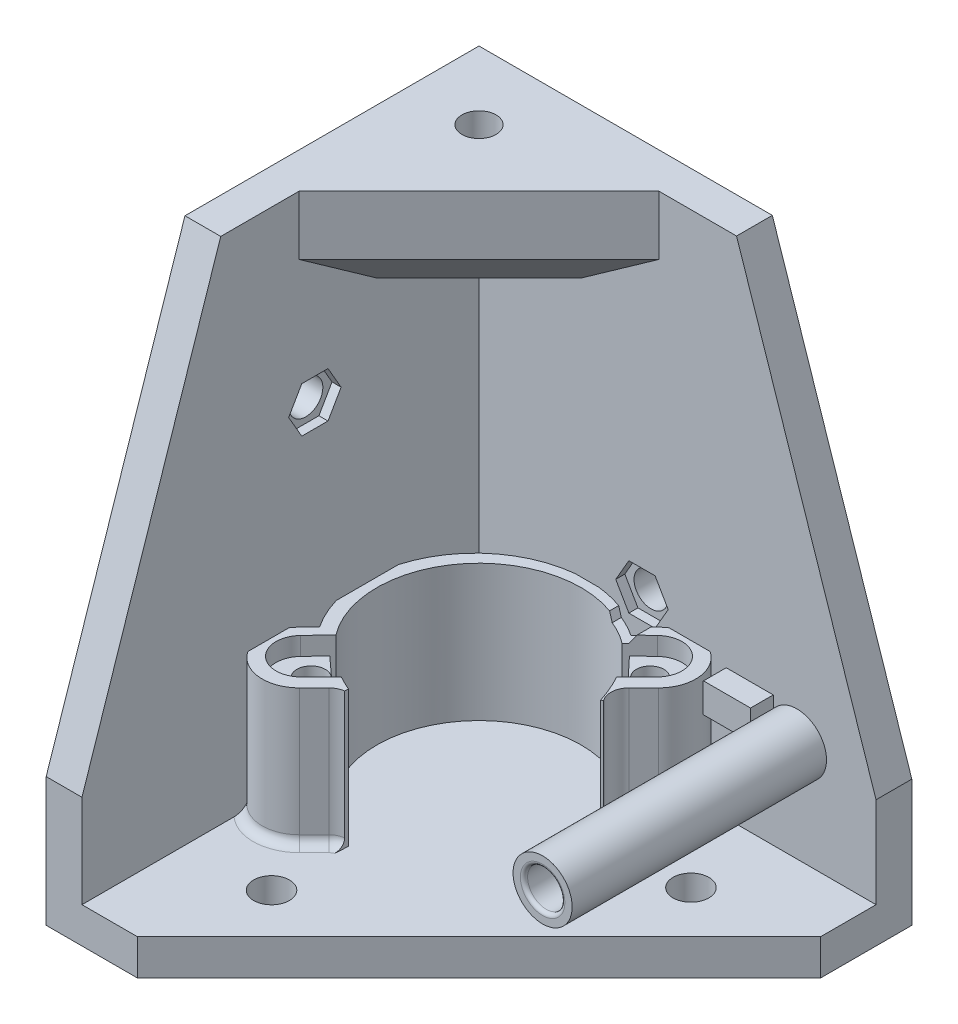
SolidWorks part; units mm, degrees
ref_plane "Front" through (0, 0, 0) normal (0, 0, 1) x (1, 0, 0)
ref_plane "Top" through (0, 0, 0) normal (0, 1, 0) x (1, 0, 0)
ref_plane "Right" through (0, 0, 0) normal (1, 0, 0) x (0, 0, -1)
sketch "Sketch1" plane through (0, 0, 0) normal (0, 1, 0) x (1, 0, 0)
  line L0 (0, 0) -> (0, 60.5)
  line L1 (0, -55) -> (0, 55) construction
  line L2 (0, 60.5) -> (60.5, 60.5)
  line L3 (60.5, 60.5) -> (60.5, 47.75)
  line L4 (60.5, 47.75) -> (12.75, 0)
  line L5 (-55, 0) -> (55, 0) construction
  line L6 (12.75, 0) -> (0, 0)
  dimension "D1" = 60.5
  dimension "D2" = 12.75
extrude "Boss-Extrude1" add sketch "Sketch1" along normal blind 5
sketch "Sketch4" plane through (0, 0, 0) normal (-1, 0, 0) x (0, 0, 1)
  line L0 (-60.5, 5) -> (-60.5, 76.1962)
  line L1 (-60.5, 76.1962) -> (-19.4, 76.1962)
  line L2 (-19.4, 76.1962) -> (0, 18.0048)
  line L3 (0, 18.0048) -> (0, 5)
  line L4 (0, -2.75) -> (0, 2.75) construction
  line L5 (-60.5, 5) -> (0, 5) construction
  line L6 (-60.5, 5) -> (0, 5)
  dimension "D1" = 71.1962
  dimension "D2" = 41.1
  dimension "D3" = 61.34
extrude "Boss-Extrude2" add sketch "Sketch4" against normal blind 5
sketch "Sketch5" plane through (0, 0, -60.5) normal (0, 0, -1) x (-1, 0, 0)
  line L0 (0, 76.1962) -> (-41, 76.1962)
  line L1 (-41, 76.1962) -> (-60.5, 17.7009)
  line L2 (-60.5, 17.7009) -> (-60.5, 5)
  line L6 (-60.5, 0) -> (0, 0)
  line L7 (0, 0) -> (0, 76.1962)
  line L8 (0, 76.1962) -> (-5, 76.1962)
  line L9 (-5, 76.1962) -> (-5, 5)
  line L10 (-5, 5) -> (-60.5, 5)
  line L11 (-60.5, 5) -> (-60.5, 0)
  line L12 (-60.5, 0) -> (0, 0)
  line L13 (0, 0) -> (0, 76.1962)
  line L14 (0, 76.1962) -> (-5, 76.1962)
  line L15 (-5, 76.1962) -> (-5, 5)
  line L16 (-5, 5) -> (-60.5, 5)
  line L17 (-60.5, 5) -> (-60.5, 0)
  line M13 (-5, 76.1962) -> (-5, 5)
  line M14 (-5, 5) -> (-60.5, 5)
  dimension "D2" = 41
  dimension "D3" = 61.66
  dimension "D1" = 0
extrude "Boss-Extrude3" add sketch "Sketch5" against normal blind 5 contours L1 L2 L0 M14 M13 region at (29.1655, 37.8824, -60.5)
sketch "Sketch6" plane through (0, 5, 0) normal (0, 1, 0) x (1, 0, 0)
  line L0 (60.5, 60.5) -> (0, 60.5) construction
  line L4 (0, 19.4) -> (0, 0)
  line L5 (60.5, 55.5) -> (5, 55.5)
  line L6 (5, 55.5) -> (5, 0)
  line L7 (5, 0) -> (12.75, 0)
  line L8 (12.75, 0) -> (60.5, 47.75)
  line L9 (60.5, 47.75) -> (60.5, 55.5)
  line L10 (60.5, 55.5) -> (5, 55.5)
  line L11 (5, 55.5) -> (5, 0)
  line L12 (5, 0) -> (12.75, 0)
  line L13 (12.75, 0) -> (60.5, 47.75)
  line L14 (60.5, 47.75) -> (60.5, 55.5)
  line L15 (0, 0) -> (5, 0)
  line L16 (5, 0) -> (5, 19.4)
  line L17 (5, 19.4) -> (0, 19.4)
  line L18 (0, 19.4) -> (0, 0)
  line L19 (0, 0) -> (5, 0)
  line L20 (5, 0) -> (5, 19.4)
  line L21 (5, 19.4) -> (0, 19.4)
  line L24 (0, 60.5) -> (0, 19.4)
  line L25 (0, 19.4) -> (5, 19.4)
  line L26 (5, 19.4) -> (5, 55.5)
  line L27 (5, 55.5) -> (41, 55.5)
  line L28 (41, 55.5) -> (41, 60.5)
  line L29 (41, 60.5) -> (0, 60.5)
  line L30 (0, 60.5) -> (0, 19.4)
  line L31 (0, 19.4) -> (5, 19.4)
  line L32 (5, 19.4) -> (5, 55.5)
  line L33 (5, 55.5) -> (41, 55.5)
  line L34 (41, 55.5) -> (41, 60.5)
  line L35 (41, 60.5) -> (0, 60.5)
  circle A0 centre (16.5, 15) radius 2.5
  circle A1 centre (45.5, 44.625) radius 2.5
  dimension "D1" = 5
  dimension "D2" = 5
  dimension "D3" = 0
  dimension "D4" = 15
  dimension "D6" = 16.5
  dimension "D7" = 15
  dimension "D9" = 15.875
  dimension "D5" = 0
  dimension "D8" = 0
extrude "Cut-Extrude1" cut sketch "Sketch6" against normal through all contours A0 | A1 region at (16.5, 5, -15) region at (45.5, 5, -44.625)
sketch "Sketch9" plane through (0, 0, -55.5) normal (0, 0, 1) x (1, 0, 0)
  line L1 (5, 76.1962) -> (5, 5) construction
  line L5 (0, 0) -> (60.5, 0)
  line L6 (0, 76.1962) -> (0, 0)
  line L7 (41, 76.1962) -> (0, 76.1962)
  line L8 (60.5, 17.7009) -> (41, 76.1962)
  line L9 (60.5, 0) -> (60.5, 17.7009)
  line L10 (0, 0) -> (60.5, 0)
  line L11 (0, 76.1962) -> (0, 0)
  line L12 (41, 76.1962) -> (0, 76.1962)
  line L13 (60.5, 17.7009) -> (41, 76.1962)
  line L14 (60.5, 0) -> (60.5, 17.7009)
  line L15 (49.45, 19.0462) -> (49.45, 3.6199) construction
  circle A0 centre (49.45, 19.0462) radius 4.1275
  circle A1 centre (49.45, 19.0462) radius 2.6035
  dimension "D2" = 5.207
  dimension "D3" = 1.524
  dimension "D4" = 57.15
  dimension "D5" = 44.45
  dimension "D1" = 0
extrude "Boss-Extrude5" add sketch "Sketch9" along normal blind 35.56 contours A1 A0 region at (45.4392, 19.0462, -55.5)
fillet "Fillet1" radius 0.508 1 edges at (52.0535, 19.0462, -19.94)
sketch "Sketch14" plane through (0, 5, 0) normal (0, 1, 0) x (1, 0, 0)
  line L0 (13.4627, 27.5396) -> (14.7681, 26.7924)
  line L1 (12.75, 0) -> (60.5, 47.75) construction
  line L2 (36.625, 23.875) -> (5, 55.5) construction
  line L3 (5, 55.5) -> (60.5, 55.5) construction
  line L4 (32.9604, 47.0373) -> (33.7076, 45.7319)
  line L5 (14.8281, 26.8523) -> (11.8274, 23.8516)
  line L6 (6.723, 28.8027) -> (9.1327, 31.3641)
  line L7 (33.6477, 45.6719) -> (36.6484, 48.6726)
  line L8 (31.6973, 53.777) -> (29.1359, 51.3673)
  line L9 (15.0744, 24.4582) -> (13.006, 22.3898)
  line L10 (5.6561, 29.7396) -> (7.0609, 31.1444)
  line L11 (36.0418, 45.4256) -> (38.1102, 47.494)
  line L12 (30.7604, 54.8439) -> (28.83, 52.9135)
  line L13 (18.1324, 24.8665) -> (30.5234, 17.7734)
  line L14 (35.6335, 42.3676) -> (42.7266, 29.9766)
  line L15 (31.7409, 18.9909) -> (18.852, 25.7543)
  line L16 (41.5091, 28.7591) -> (34.7457, 41.648)
  line L17 (16.5689, 25.6946) -> (16.5343, 25.1798)
  line L18 (34.7457, 41.648) -> (35.7996, 42.0774)
  circle A0 centre (20.5607, 39.9393) radius 14.2875
  arc A1 (11.8274, 23.8516) -> (6.723, 28.8027) centre (9.3129, 26.3661) cw
  arc A2 (36.6484, 48.6726) -> (31.6973, 53.777) centre (34.1339, 51.1871) ccw
  arc A3 (13.006, 22.3898) -> (5.6561, 29.7396) centre (9.3311, 26.0647) cw
  arc A4 (38.1102, 47.494) -> (30.7604, 54.8439) centre (34.4353, 51.1689) ccw
  arc A5 (7.0609, 31.1444) -> (28.83, 52.9135) centre (20.0709, 39.9035) cw
  arc A6 (36.0418, 45.4256) -> (35.6335, 42.3676) centre (37.8378, 43.6295) ccw
  arc A7 (15.0744, 24.4582) -> (18.1324, 24.8665) centre (16.8705, 22.6622) cw
  arc A9 (33.8602, 45.8844) -> (36.3595, 38.5726) centre (13.6025, 34.877) cw
  arc A10 (14.6156, 26.6398) -> (21.9274, 24.1405) centre (25.623, 46.8975) ccw
  point P40 (34.6689, 44.0527)
  point P43 (16.4473, 25.8311)
  line M13 (60.5, 55.5) -> (5, 55.5)
  line M14 (5, 55.5) -> (5, 0)
  line M16 (12.75, 0) -> (60.5, 47.75)
  dimension "D1" = 28.575
  dimension "D2" = 3.556
  dimension "D3" = 2.54
extrude "Boss-Extrude6" add sketch "Sketch14" along normal blind 19.05 contours L2 A0 L5 A1 L6 A5 L10 A3 L9 A7 L13 M16 M14 | L2 L14 A6 L11 A4 L12 A5 A0 L8 A2 L7 M16 M13 region at (7.691, 5, -30.3062) region at (10.0875, 5, -50.8829)
sketch "Sketch15" plane through (0, 76.1962, 0) normal (0, 1, 0) x (1, 0, 0)
  line L0 (5, 30.3375) -> (30.1625, 55.5)
  line L1 (0, -33.275) -> (0, 33.275) construction
  line L2 (41, 60.5) -> (0, 60.5) construction
  line L6 (0, 60.5) -> (0, 19.4)
  line L7 (0, 19.4) -> (5, 19.4)
  line L8 (5, 19.4) -> (5, 55.5)
  line L9 (5, 55.5) -> (41, 55.5)
  line L10 (41, 55.5) -> (41, 60.5)
  line L11 (41, 60.5) -> (0, 60.5)
  line L13 (0, 19.4) -> (5, 19.4)
  line L14 (5, 30.3375) -> (5, 55.5)
  line L15 (5, 55.5) -> (30.1625, 55.5)
  line L16 (41, 55.5) -> (41, 60.5)
  circle A0 centre (9.525, 50.975) radius 2.3812
  line M11 (5, 19.4) -> (5, 55.5)
  line M12 (5, 55.5) -> (41, 55.5)
  dimension "D3" = 4.7625
  dimension "D4" = 9.525
  dimension "D5" = 9.525
  dimension "D2" = 45
  dimension "D1" = 0
extrude "Boss-Extrude7" add sketch "Sketch15" against normal blind 15.875 contours L0 A0 M11 M12 region at (13.6178, 76.1962, -46.8822)
chamfer "Chamfer2" distance 7.62 angle 45 1 edges at (17.5813, 60.3212, -42.9187)
fillet "Fillet2" radius 1.27 7 edges at (39.6065, 5, -51.6871) (37.076, 5, -46.4598) (35.3202, 5, -43.9657) (8.8129, 5, -20.8935) (14.0402, 5, -23.424) (15.745, 5, -24.9392) (35.7165, 5, -42.2225)
sketch "Sketch16" plane through (0, 0, -55.5) normal (0, 0, 1) x (1, 0, 0)
  line L1 (46.1305, 23.2107) -> (38.2864, 23.2107)
  line L2 (46.1305, 23.2107) -> (46.1305, 19.0978)
  line L3 (46.1305, 19.0978) -> (38.2864, 19.0978)
  line L4 (38.2864, 23.2107) -> (38.2864, 19.0978)
extrude "Boss-Extrude8" add sketch "Sketch16" along normal blind 3.175
chamfer "Chamfer3" distance 1.27 angle 45 1 edges at (38.2864, 23.2107, -55.0794)
sketch "Sketch17" plane through (0, 5, 0) normal (0, 1, 0) x (1, 0, 0)
  line L0 (8.716, 30.9212) -> (14.047, 26.0712)
  line L1 (36.625, 23.875) -> (5, 55.5) construction
  line L2 (12.75, 0) -> (60.5, 47.75) construction
  line L3 (5, 55.5) -> (18.418, 55.5) construction
  line L4 (5, 55.5) -> (5, 44.2452) construction
  line L5 (29.6632, 51.8634) -> (34.5959, 46.6202)
  line L22 (37.3079, 55.5) -> (31.5627, 55.5)
  line L23 (30.7604, 54.8439) -> (28.83, 52.9135)
  line L24 (21.7238, 55.5) -> (18.418, 55.5)
  line L25 (5, 44.2452) -> (5, 35.5618)
  line L26 (7.0609, 31.1444) -> (5.6561, 29.7396)
  line L27 (5, 28.9373) -> (5, 23.1921)
  line L28 (13.006, 22.3898) -> (15.0744, 24.4582)
  line L29 (16.5343, 25.1798) -> (16.5689, 25.6946)
  line L30 (16.5343, 25.1798) -> (16.5689, 25.6946)
  line L31 (35.539, 41.9712) -> (35.7996, 42.0774)
  line L32 (35.539, 41.9712) -> (35.7996, 42.0774)
  line L33 (14.6156, 26.6398) -> (11.8274, 23.8516)
  line L34 (6.723, 28.8027) -> (9.1327, 31.3641)
  line L35 (29.1359, 51.3673) -> (31.6973, 53.777)
  line L36 (36.6484, 48.6726) -> (33.8602, 45.8844)
  line L40 (35.7996, 42.0774) -> (35.6335, 42.3676)
  line L41 (36.0418, 45.4256) -> (38.1102, 47.494)
  line L43 (37.3079, 55.5) -> (31.5627, 55.5)
  line L44 (30.7604, 54.8439) -> (28.83, 52.9135)
  line L45 (21.7238, 55.5) -> (18.418, 55.5)
  line L46 (5, 44.2452) -> (5, 35.5618)
  line L47 (7.0609, 31.1444) -> (5.6561, 29.7396)
  line L48 (5, 28.9373) -> (5, 23.1921)
  line L49 (13.006, 22.3898) -> (15.0744, 24.4582)
  line L54 (14.6156, 26.6398) -> (11.8274, 23.8516)
  line L55 (6.723, 28.8027) -> (9.1327, 31.3641)
  line L56 (29.1359, 51.3673) -> (31.6973, 53.777)
  line L57 (36.6484, 48.6726) -> (33.8602, 45.8844)
  line L61 (35.7996, 42.0774) -> (35.6335, 42.3676)
  line L62 (36.0418, 45.4256) -> (38.1102, 47.494)
  circle A1 centre (33.6908, 50.7324) radius 2.1828
  circle A2 centre (10.0204, 27.0078) radius 1.9844
  circle A3 centre (33.6908, 50.7324) radius 1.9288
  arc A15 (38.1102, 47.494) -> (37.3079, 55.5) centre (34.4353, 51.1689) ccw
  arc A17 (31.5627, 55.5) -> (30.7604, 54.8439) centre (34.4353, 51.1689) ccw
  arc A18 (28.83, 52.9135) -> (21.7238, 55.5) centre (20.0709, 39.9035) ccw
  arc A19 (18.418, 55.5) -> (5, 44.2452) centre (20.0709, 39.9035) ccw
  arc A20 (5, 35.5618) -> (7.0609, 31.1444) centre (20.0709, 39.9035) ccw
  arc A21 (5.6561, 29.7396) -> (5, 28.9373) centre (9.3311, 26.0647) ccw
  arc A22 (5, 23.1921) -> (13.006, 22.3898) centre (9.3311, 26.0647) ccw
  arc A23 (16.5343, 25.1798) -> (15.0744, 24.4582) centre (16.8705, 22.6622) ccw
  arc A24 (14.6156, 26.6398) -> (16.5689, 25.6946) centre (25.623, 46.8975) ccw
  arc A25 (6.723, 28.8027) -> (11.8274, 23.8516) centre (9.3129, 26.3661) ccw
  arc A26 (29.1359, 51.3673) -> (9.1327, 31.3641) centre (20.5607, 39.9393) ccw
  arc A27 (36.6484, 48.6726) -> (31.6973, 53.777) centre (34.1339, 51.1871) ccw
  arc A28 (35.539, 41.9712) -> (33.8602, 45.8844) centre (13.6025, 34.877) ccw
  arc A29 (36.0418, 45.4256) -> (35.6335, 42.3676) centre (37.8378, 43.6295) ccw
  arc A30 (38.1102, 47.494) -> (37.3079, 55.5) centre (34.4353, 51.1689) ccw
  arc A32 (31.5627, 55.5) -> (30.7604, 54.8439) centre (34.4353, 51.1689) ccw
  arc A33 (28.83, 52.9135) -> (21.7238, 55.5) centre (20.0709, 39.9035) ccw
  arc A34 (18.418, 55.5) -> (5, 44.2452) centre (20.0709, 39.9035) ccw
  arc A35 (5, 35.5618) -> (7.0609, 31.1444) centre (20.0709, 39.9035) ccw
  arc A36 (5.6561, 29.7396) -> (5, 28.9373) centre (9.3311, 26.0647) ccw
  arc A37 (5, 23.1921) -> (13.006, 22.3898) centre (9.3311, 26.0647) ccw
  arc A38 (16.5343, 25.1798) -> (15.0744, 24.4582) centre (16.8705, 22.6622) ccw
  arc A39 (14.6156, 26.6398) -> (16.5689, 25.6946) centre (25.623, 46.8975) ccw
  arc A40 (6.723, 28.8027) -> (11.8274, 23.8516) centre (9.3129, 26.3661) ccw
  arc A41 (29.1359, 51.3673) -> (9.1327, 31.3641) centre (20.5607, 39.9393) ccw
  arc A42 (36.6484, 48.6726) -> (31.6973, 53.777) centre (34.1339, 51.1871) ccw
  arc A43 (35.539, 41.9712) -> (33.8602, 45.8844) centre (13.6025, 34.877) ccw
  arc A44 (36.0418, 45.4256) -> (35.6335, 42.3676) centre (37.8378, 43.6295) ccw
  line M44 (33.8602, 45.8844) -> (36.6484, 48.6726)
  arc M45 (36.6484, 48.6726) -> (31.6973, 53.777) centre (34.1339, 51.1871) ccw
  line M46 (31.6973, 53.777) -> (29.1359, 51.3673)
  line M48 (9.1327, 31.3641) -> (6.723, 28.8027)
  arc M49 (6.723, 28.8027) -> (11.8274, 23.8516) centre (9.3129, 26.3661) ccw
  line M50 (11.8274, 23.8516) -> (14.6156, 26.6398)
  dimension "D2" = 3.9688
  dimension "D3" = 0.254
  dimension "D1" = 0
extrude "Boss-Extrude9" add sketch "Sketch17" along normal offset from surface (16.51 mm away) 2.54 contours L5 A1 M46 M44 M45 | L0 M48 M49 M50 | A1 L5 A3 region at (11.3737, 5, -28.4876) region at (30.7585, 5, -52.737) region at (33.0584, 5, -52.7569) up to face at (20.9693, 24.05, -39.9839)
sketch "Sketch18" plane through (0, 0, 0) normal (-1, 0, 0) x (0, 0, 1)
  line L0 (-60.5, 76.1962) -> (-60.5, 0) construction
  line L1 (33.275, 0) -> (-33.275, 0) construction
  circle A0 centre (-32.56, 49.53) radius 2.3813
  dimension "D1" = 27.94
  dimension "D2" = 49.53
  dimension "D3" = 4.7625
extrude "Cut-Extrude2" cut sketch "Sketch18" against normal up to next
sketch "Sketch19" plane through (0, 0, -60.5) normal (0, 0, -1) x (-1, 0, 0)
  line L0 (0, 33.275) -> (0, -33.275) construction
  line L1 (33.275, 0) -> (-33.275, 0) construction
  circle A0 centre (-27.7812, 26.1937) radius 2.3813
  dimension "D1" = 27.7812
  dimension "D2" = 26.1937
  dimension "D3" = 4.7625
extrude "Cut-Extrude3" cut sketch "Sketch19" against normal up to next
sketch "Sketch20" plane through (0, 0, -55.5) normal (0, 0, 1) x (1, 0, 0)
  line L1 (31.4474, 26.1937) -> (29.6143, 29.3687)
  line L2 (29.6143, 29.3687) -> (25.9482, 29.3687)
  line L3 (25.9482, 29.3687) -> (24.1151, 26.1937)
  line L4 (24.1151, 26.1937) -> (25.9482, 23.0187)
  line L5 (25.9482, 23.0187) -> (29.6143, 23.0187)
  line L6 (29.6143, 23.0187) -> (31.4474, 26.1937)
  circle A0 centre (27.7812, 26.1937) radius 2.3813 construction
  circle A1 centre (27.7812, 26.1937) radius 2.3813
  circle A2 centre (27.7812, 26.1937) radius 3.175 construction
  dimension "D1" = 6.35
extrude "Cut-Extrude4" cut sketch "Sketch20" against normal blind 1.27 and the other way up to vertex (4.1327 mm away) contours L1 L2 L3 L4 L5 L6 other way up to point (29.1359, 24.05, -51.3673)
sketch "Sketch21" plane through (5, 0, 0) normal (1, 0, 0) x (0, 0, -1)
  line L1 (34.3931, 52.705) -> (30.7269, 52.705)
  line L2 (30.7269, 52.705) -> (28.8938, 49.53)
  line L3 (28.8938, 49.53) -> (30.7269, 46.355)
  line L4 (30.7269, 46.355) -> (34.3931, 46.355)
  line L5 (34.3931, 46.355) -> (36.2262, 49.53)
  line L6 (36.2262, 49.53) -> (34.3931, 52.705)
  circle A0 centre (32.56, 49.53) radius 2.3813 construction
  circle A1 centre (32.56, 49.53) radius 2.3812
  circle A2 centre (32.56, 49.53) radius 3.175 construction
  dimension "D1" = 6.35
extrude "Cut-Extrude5" cut sketch "Sketch21" against normal blind 1.27 contours L1 L2 L3 L4 L5 L6
sketch "Sketch23" plane through (0, 0, 0) normal (0, 1, 0) x (1, 0, 0)
  line L1 (60.5, 60.5) -> (101.14, 60.5)
  line L2 (60.5, 60.5) -> (60.5, 24.94)
  line L3 (60.5, 24.94) -> (101.14, 24.94)
  line L4 (101.14, 60.5) -> (101.14, 24.94)
  dimension "D1" = 40.64
  dimension "D2" = 35.56
extrude "Boss-Extrude12" [suppressed] add sketch "Sketch23" along normal blind 5.08
sketch "Sketch24" [suppressed] plane through (0, 5.08, 0) normal (0, 1, 0) x (1, 0, 0)
  line L0 (101.14, 60.5) -> (60.5, 60.5) construction
  line L1 (60.5, 47.75) -> (60.5, 55.5) construction
  circle A0 centre (65.58, 55.42) radius 1.7145
  circle A1 centre (96.06, 55.42) radius 1.7145
  circle A2 centre (96.06, 29.258) radius 1.7145
  circle A3 centre (65.58, 29.258) radius 1.7145
  dimension "D1" = 3.429
  dimension "D2" = 26.162
  dimension "D3" = 30.48
  dimension "D4" = 5.08
  dimension "D5" = 5.08
extrude "Cut-Extrude6" [suppressed] cut sketch "Sketch24" against normal up to next
